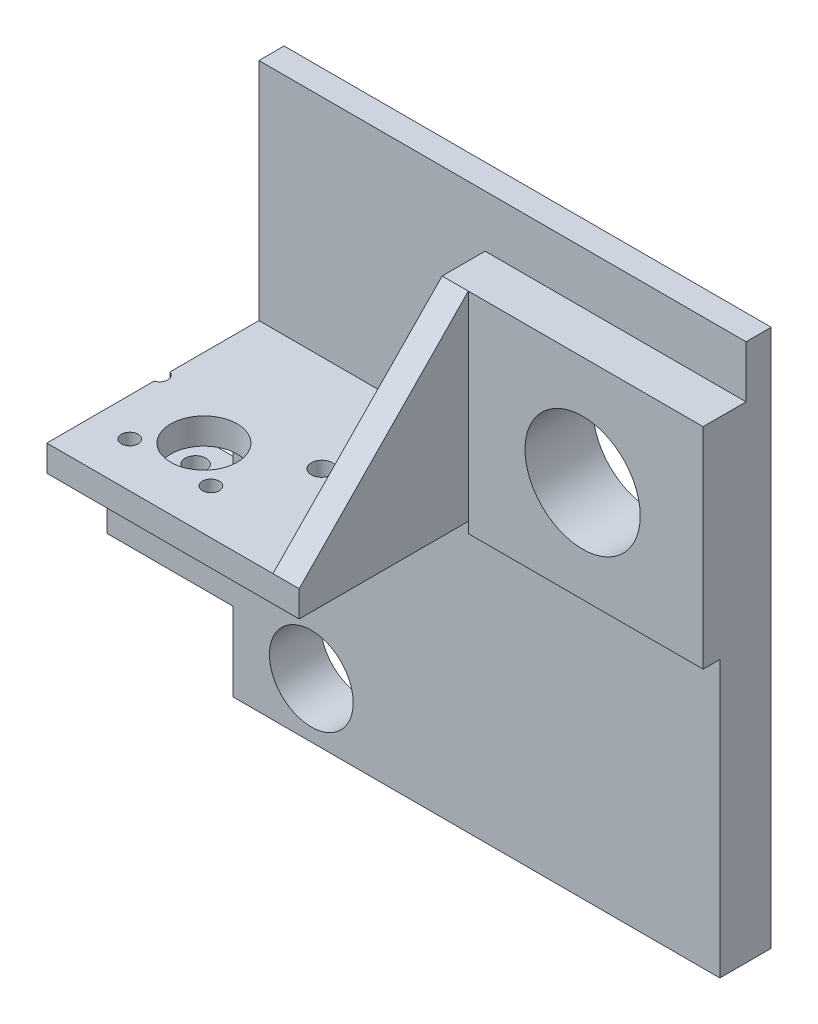
SolidWorks part; units mm, degrees
material "ABS"
ref_plane "Front Plane" through (0, 0, 0) normal (0, 0, 1) x (1, 0, 0)
ref_plane "Top Plane" through (0, 0, 0) normal (0, 1, 0) x (1, 0, 0)
ref_plane "Right Plane" through (0, 0, 0) normal (1, 0, 0) x (0, 0, -1)
sketch "Sketch1" plane through (0, 0, 0) normal (0, 0, 1) x (1, 0, 0)
  line L0 (-24, 15) -> (0, 15)
  line L1 (0, 15) -> (0, 0)
  line L2 (0, 0) -> (93, 0)
  line L3 (93, 0) -> (93, 102.7)
  line L4 (93, 102.7) -> (0, 102.7)
  line L5 (0, 102.7) -> (0, 30)
  line L6 (0, 30) -> (-24, 30)
  line L7 (-24, 30) -> (-24, 15)
  circle A0 centre (15, 10.5) radius 8
  circle A1 centre (70, 72) radius 11
  circle A2 centre (15, 10.5) radius 11
  dimension "D1" = 15
  dimension "D10" = 16
  dimension "D11" = 22
  dimension "D12" = 22
  dimension "D2" = 24
  dimension "D3" = 72.7
  dimension "D4" = 15
  dimension "D5" = 15
  dimension "D6" = 10.5
  dimension "D7" = 82.5061
  dimension "D8" = 72
  dimension "D9" = 93
extrude "Boss-Extrude1" add sketch "Sketch1" along normal blind 4.8 contours A2 L2 L3 L4 L5 L6 L7 L0 L1 A1 | L2 A2 A0 region at (44.5238, 51.0418, 0) region at (8.6656, 19.1141, 0)
sketch "Sketch2" plane through (0, 0, 4.8) normal (0, 0, 1) x (1, 0, 0)
  line L0 (93, 0) -> (93, 102.7) construction
  line L1 (48.1786, 92.7632) -> (93, 92.7632)
  line L2 (48.1786, 92.7632) -> (48.1786, 52.666)
  line L3 (48.1786, 52.666) -> (93, 52.666)
  line L4 (93, 92.7632) -> (93, 52.666)
  line L5 (48.1786, 92.7632) -> (93, 52.666) construction
  line L6 (48.1786, 52.666) -> (93, 92.7632) construction
  circle A0 centre (70, 72) radius 11
  circle A1 centre (70, 72) radius 4.15
  point P8 (70.5893, 72.7146)
  line M4 (93, 0) -> (93, 102.7)
  circle M10 centre (70, 72) radius 11
  dimension "D1" = 22
  dimension "D2" = 8.3
extrude "Boss-Extrude2" add sketch "Sketch2" along normal blind 8.2 contours L2 L3 L1 M4 M10 region at (70.5893, 92.1618, 4.8)
sketch "Sketch3" plane through (0, 0, 4.8) normal (0, 0, 1) x (1, 0, 0)
  line L1 (-24, 15) -> (0, 15)
  line L2 (-24, 15) -> (-24, 30)
  line L3 (-24, 30) -> (0, 30)
  line L4 (0, 15) -> (0, 30)
  line L5 (-24, 15) -> (0, 30) construction
  line L6 (-24, 30) -> (0, 15) construction
  line L7 (0, 0) -> (93, 0)
  line L8 (0, 0) -> (0, 52.666)
  line L9 (0, 52.666) -> (93, 52.666)
  line L10 (93, 0) -> (93, 52.666)
  line L11 (0, 0) -> (93, 52.666) construction
  line L12 (0, 52.666) -> (93, 0) construction
  circle A0 centre (15, 10.5) radius 8
  point P4 (-12, 22.5)
  point P11 (46.5, 26.333)
  circle M1 centre (15, 10.5) radius 8
  line M6 (0, 102.7) -> (0, 30)
  line M7 (0, 30) -> (-24, 30)
  line M8 (-24, 30) -> (-24, 15)
  line M9 (-24, 15) -> (0, 15)
  line M10 (0, 15) -> (0, 0)
  line M11 (0, 0) -> (93, 0)
  line M12 (93, 0) -> (93, 52.666)
  line M13 (93, 52.666) -> (48.1786, 52.666)
extrude "Boss-Extrude3" add sketch "Sketch3" along normal blind 5 contours L4 M9 M7 M8 | L9 L4 M6 M10 M11 M12 M13 M1 region at (-12, 22.5, 4.8) region at (47.8484, 27.0108, 4.8)
sketch "Sketch4" plane through (0, 59.701, 0) normal (0, -1, 0) x (1, 0, 0)
  line L0 (0, 9.8) -> (0, 4.8) construction
  line L1 (0, 4.8) -> (48.1786, 4.8)
  line L2 (0, 4.8) -> (0, 45.3)
  line L3 (0, 45.3) -> (48.1786, 45.3)
  line L4 (48.1786, 4.8) -> (48.1786, 45.3)
  line L5 (0, 4.8) -> (48.1786, 45.3) construction
  line L6 (0, 45.3) -> (48.1786, 4.8) construction
  line L7 (0, 4.8) -> (48.1786, 4.8) construction
  line L8 (48.1786, 13) -> (48.1786, 9.8) construction
  line L9 (0, 0) -> (93, 0) construction
  line L10 (0, 45.3) -> (-5, 45.3)
  line L11 (0, 45.3) -> (0, 0)
  line L12 (0, 0) -> (-5, 0)
  line L13 (-5, 45.3) -> (-5, 0)
  line L14 (0, 45.3) -> (-5, 0) construction
  line L15 (0, 0) -> (-5, 45.3) construction
  circle A0 centre (15, 30.3) radius 6.35
  circle A1 centre (15, 23.3) radius 18.5
  circle A3 centre (30.5, 23.3) radius 2
  circle A4 centre (22.75, 9.8766) radius 2
  circle A5 centre (7.25, 9.8766) radius 2
  point P10 (24.0893, 25.05)
  point P30 (-2.5, 22.65)
  arc M5 (6.0925, 30.9329) -> (23.9075, 30.9329) centre (15, 30.3) ccw
  arc M7 (24.2388, 31.0672) -> (5.7612, 31.0672) centre (15, 23.3) cw
  circle M9 centre (22.75, 9.8766) radius 1.6
  circle M10 centre (7.25, 9.8766) radius 1.6
  circle M11 centre (-0.5, 23.3) radius 1.6
  circle M12 centre (7.25, 36.7234) radius 1.6
  circle M13 centre (22.75, 36.7234) radius 1.6
  circle M15 centre (28.4234, 31.05) radius 2.1
  circle M16 centre (1.5766, 31.05) radius 2.1
  circle M17 centre (15, 7.8) radius 2.1
  circle M19 centre (15, 23.3) radius 18.5
  dimension "D1" = 12.7
  dimension "D2" = 15
  dimension "D3" = 4
  dimension "D4" = 4
  dimension "D5" = 4
  dimension "D6" = 5
  dimension "D7" = 0
extrude "Boss-Extrude4" add sketch "Sketch4" along normal blind 5 contours L1 L4 L3 M19 | A0 L3 L2 A5 A4 A3 M12 M19 M16 M11 M13 M17 M15 M5 M7 | M5 M7 | M17 | A4 M9 | M9 | M10 | A5 M10 | M15 | L2 M16 | L2 L1 M19 region at (3.5769, 59.701, 6.9879) region at (34.3513, 59.701, 27.7532) region at (15.8399, 59.701, 22.3532) region at (1.715, 59.701, 31.05) region at (20.8066, 59.701, 9.8766) region at (5.3066, 59.701, 9.8766) region at (22.75, 59.701, 9.8766) region at (7.25, 59.701, 9.8766) region at (28.4234, 59.701, 31.05) region at (15, 59.701, 7.8)
sketch "Sketch5" plane through (48.1786, 0, 0) normal (1, 0, 0) x (0, 0, -1)
  line L0 (-45.3, 59.701) -> (-13, 92.7632)
  line L1 (-13, 92.7632) -> (-4.8, 92.7632)
  line L2 (-4.8, 92.7632) -> (-4.8, 54.701)
  line L3 (-4.8, 54.701) -> (-45.3, 54.701)
  line L4 (-45.3, 54.701) -> (-45.3, 59.701)
extrude "Boss-Extrude5" add sketch "Sketch5" against normal blind 5
sketch "Sketch6" plane through (0, 0, 4.8) normal (0, 0, 1) x (1, 0, 0)
  line L0 (0, 54.701) -> (0, 52.666) construction
  line L1 (0, 54.701) -> (48.1786, 54.701)
  line L2 (0, 54.701) -> (0, 52.666)
  line L3 (0, 52.666) -> (48.1786, 52.666)
  line L4 (48.1786, 54.701) -> (48.1786, 52.666)
  line L5 (0, 54.701) -> (48.1786, 52.666) construction
  line L6 (0, 52.666) -> (48.1786, 54.701) construction
  line L7 (0, 54.701) -> (48.1786, 54.701) construction
  point P4 (24.0893, 53.6835)
extrude "Boss-Extrude6" add sketch "Sketch6" along normal up to surface (5 mm away) up to face at (20.6865, 27.5553, 9.8)
ref_plane "Plane1" through (8.4954, 19.8501, 33.6927) normal (0.5478, -0.7861, -0.2862) x (-0.8366, -0.5147, -0.1874)
sketch "Sketch8" plane through (0, 30, 0) normal (0, 1, 0) x (1, 0, 0)
  line L0 (0, 0) -> (-24, -9.8)
  line L1 (-24, -9.8) -> (-24, 0)
  line L2 (-24, 0) -> (0, -9.8)
  circle A0 centre (-12, -4.9) radius 2
  dimension "D1" = 4
extrude "Cut-Extrude1" cut sketch "Sketch8" against normal through all contours A0
